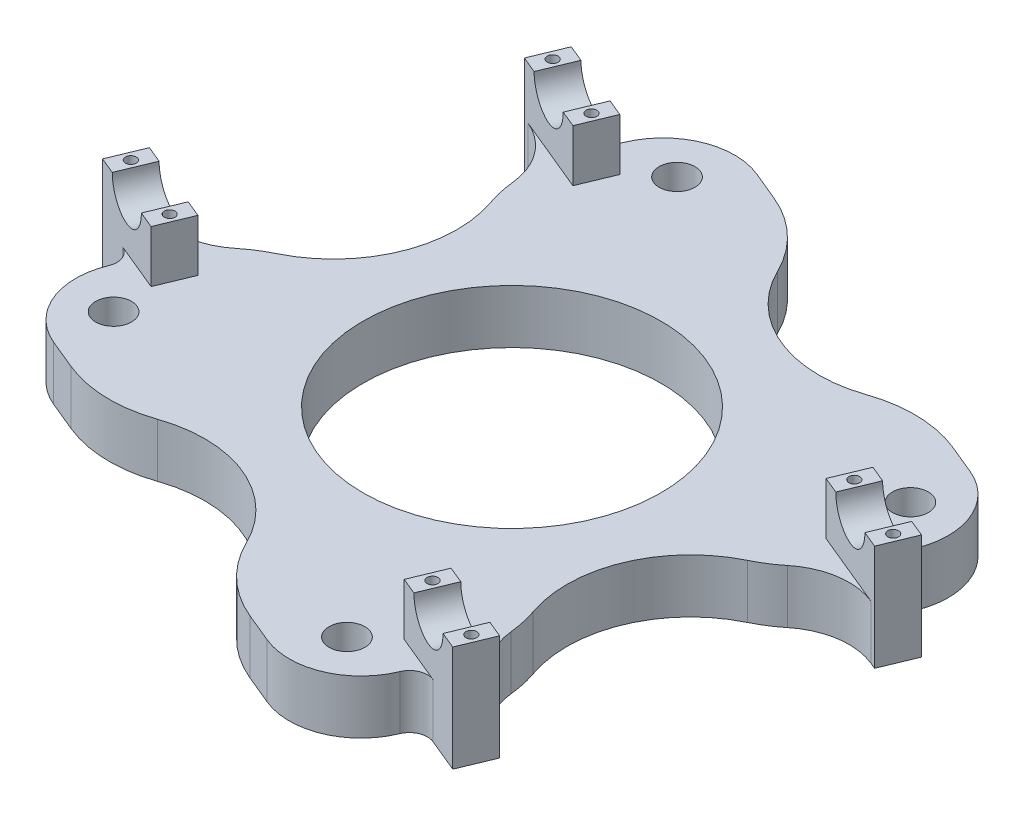
SolidWorks part; units mm, degrees
note: '?' marks a value the reader was unsure of.
material "6063-T5"
ref_plane "Front Plane" through (0, 0, 0) normal (0, 0, 1) x (1, 0, 0)
ref_plane "Top Plane" through (0, 0, 0) normal (0, 1, 0) x (1, 0, 0)
ref_plane "Right Plane" through (0, 0, 0) normal (1, 0, 0) x (0, 0, -1)
sketch "Sketch1" plane through (0, 0, 0) normal (0, 1, 0) x (1, 0, 0)
  circle A0 centre (0, 0) radius 41.5
  circle A1 centre (0, 0) radius 45.5
  dimension "D1" = 83
  dimension "D2" = 91
extrude "Boss-Extrude1" add sketch "Sketch1" along normal blind 156.5
ref_axis "Axis1" through (0, -7.993, 0) along (0, 1, 0)?
ref_plane "Plane1" through (0, 0, 0) normal (0.7071, 0, 0.7071) x (0, 1, 0)
sketch "Sketch3" plane through (0, 0, 0) normal (0.7071, 0, 0.7071) x (0, 1, 0)
  line L0 (0, 0) -> (152.25, 0)
  circle A0 centre (152.25, 0) radius 1.75
  dimension "D1" = 152.25
extrude "Cut-Extrude2" cut sketch "Sketch3" against normal through all and the other way through all contours A0
pattern_circular "CirPattern2" count 8 over 360 about axis through (0, -7.993, 0) along (0, 1, 0) of "Cut-Extrude2"
ref_plane "Plane2" through (0, 0, 0) normal (0.9239, 0, 0.3827) x (0, 1, 0)
ref_plane "Plane4" through (0, 0, 0) normal (0.3827, 0, -0.9239) x (0, 1, 0)
sketch "Sketch6" plane through (0, 0, 0) normal (0.9239, 0, 0.3827) x (0, 1, 0)
  line L0 (0, 0) -> (58, 0)
  line L1 (58, 0) -> (133, 0)
  line L3 (133, 0) -> (133, -38.75)
  line L4 (58, 38.516) -> (133, 38.516)
  line L5 (58, 38.516) -> (58, -38.75)
  line L6 (133, 38.516) -> (133, -38.75)
  line L7 (58, -38.75) -> (133, -38.75)
  line L8 (58, 38.516) -> (133, -38.75) construction
  line L9 (133, 38.516) -> (58, -38.75) construction
  point P6 (95.5, -0.117)
  dimension "D1" = 58
  dimension "D2" = 75
  dimension "D3" = 38.75
extrude "Cut-Extrude5" cut sketch "Sketch6" against normal through all contours L6 L4 L5 L7
fillet "Fillet1" radius 20 1 edges at (-3.0493, 58, -43.2058)
fillet "Fillet2" radius 20 1 edges at (-3.0493, 133, -43.2058)
fillet "Fillet3" radius 20 1 edges at (-33.0671, 58, 27.9926)
fillet "Fillet4" radius 20 1 edges at (-33.0671, 133, 27.9926)
sketch "Sketch11" plane through (0, 0, 0) normal (0.3827, 0, -0.9239) x (0, 1, 0)
  line L0 (0, 0) -> (0, 45.5)
  line L1 (0, 45.5) -> (15, 45.5)
  line L2 (156.5, 45.5) -> (0, 45.5) construction
  line L3 (15, 45.5) -> (15, 75)
  line L5 (0, 0) -> (15, 0)
  line L10 (0, 0) -> (0, 75)
  line L11 (0, 75) -> (15, 75)
  line L12 (15, 0) -> (15, 75)
  dimension "D1" = 15
  dimension "D2" = 29.5
extrude "Boss-Extrude2" add sketch "Sketch11" along normal blind 75 and the other way blind 75 contours L5 L12 L1 L0 | L11 L10 L1 L3
mirror "Mirror1" about plane through (0, 0, 0) normal (0.9239, 0, 0.3827) of "Boss-Extrude2"
sketch "Sketch12" plane through (0, 156.5, 0) normal (0, 1, 0) x (1, 0, 0)
  circle A0 centre (0, 0) radius 41.5
extrude "Cut-Extrude6" cut sketch "Sketch12" against normal through all
fillet "Fillet5" radius 20 1 edges at (97.9922, 7.5, -40.5897)
fillet "Fillet6" radius 20 1 edges at (40.5897, 7.5, 97.9922)
fillet "Fillet7" radius 20 1 edges at (-40.5897, 7.5, -97.9922)
fillet "Fillet8" radius 20 1 edges at (-97.9922, 7.5, 40.5897)
fillet "Fillet9" radius 25 1 edges at (0, 15, 45.5)
sketch "Sketch15" plane through (0, 15, 0) normal (0, 1, 0) x (1, 0, 0)
  line L0 (-90.3386, -22.1121) -> (-80.7715, 0.9849)
  line L1 (-90.3386, -22.1121) -> (-48.2434, 79.5146) construction
  line L2 (-48.2434, 79.5146) -> (-57.8105, 56.4176)
  line L4 (-80.7715, 0.9849) -> (-57.8105, 56.4176)
  arc A0 (-80.7715, 0.9849) -> (-57.8105, 56.4176) centre (-84.8971, 35.1655) ccw
  circle M3 centre (0, 0) radius 70.5
  line M4 (-48.2434, 79.5146) -> (-90.3386, -22.1121)
  dimension "D1" = 25
  dimension "D2" = 25
extrude "Cut-Extrude7" cut sketch "Sketch15" against normal through all and the other way through all contours A0 M3 | A0 M4 M3
fillet "Fillet10" radius 35 2 edges at (-75.4639, 15, -2.0543) (-80.7715, 7.5, -0.9849)
fillet "Fillet11" radius 35 3 edges at (-54.8137, 15, -51.9084) (-57.8105, 7.5, -56.4176) (-52.824, 18.6611, -22.6495)
pattern_circular "CirPattern4" count 4 over 360 about axis through (0, 0, 0) along (0, 1, 0) of "Cut-Extrude7", "Fillet10", "Fillet11"
sketch "Sketch16" plane through (0, 15, 0) normal (0, 1, 0) x (1, 0, 0)
  line L0 (-90.3386, -37.4195) -> (-78.5298, -32.5281)
  circle A0 centre (0, 0) radius 85
  arc A1 (-90.3386, -22.1121) -> (-79.5146, -48.2434) centre (-71.861, -29.7658) ccw construction
  circle A2 centre (-78.5298, -32.5281) radius 5
extrude "Cut-Extrude8" cut sketch "Sketch16" against normal through all contours A2
pattern_circular "CirPattern5" count 4 over 360 about axis through (0, 0, 0) along (0, 1, 0) of "Cut-Extrude8"
sketch "Sketch32" plane through (0, 15, 0) normal (0, 1, 0) x (1, 0, 0)
  circle A0 centre (0, 0) radius 138.736
extrude "Cut-Extrude20" cut sketch "Sketch32" along normal through all
ref_plane "Plane5" through (15.3073, 0, -36.9552) normal (0.3827, 0, -0.9239) x (0, 1, 0)
sketch "Sketch33" plane through (15.3073, 0, -36.9552) normal (0.3827, 0, -0.9239) x (0, 1, 0)
  line L0 (0, 0) -> (0, 77.69)
  line L1 (0, 65.19) -> (22, 65.19)
  line L2 (0, 90.19) -> (22, 90.19)
  line L3 (22, 65.19) -> (22, 90.19)
  line L4 (0, 90.19) -> (0, 65.19)
  line L5 (22, 65.19) -> (42, 65.19)
  line L6 (42, 65.19) -> (42, 90.19)
  line L7 (42, 90.19) -> (22, 90.19)
  circle A0 centre (0, 77.69) radius 12.5
  dimension "D2" = 22
  dimension "D4" = 20
  dimension "D1" = 77.69
  dimension "D3" = 22
  dimension "D5" = 20
extrude "Boss-Extrude3" add sketch "Sketch33" along normal blind 10 contours L0 A0 L4 | A0 L1 L3 L2 | L6 L7 L3 L5
sketch "Sketch34" plane through (15.3073, 0, -36.9552) normal (-0.3827, 0, 0.9239) x (0.9239, 0, 0.3827)
  line L0 (77.69, 42) -> (77.69, 29.5)
  line L1 (65.19, 42) -> (90.19, 42) construction
  circle A0 centre (77.69, 29.5) radius 7.5
  dimension "D2" = 15
  dimension "D1" = 12.5
extrude "Cut-Extrude21" cut sketch "Sketch34" against normal through all
sketch "Sketch39" plane through (0, 42, 0) normal (0, 1, 0) x (1, 0, 0)
  line L0 (75.535, 12.008) -> (98.632, 2.441)
  line L1 (98.632, 2.441) -> (102.4589, 11.6798)
  line L2 (102.4589, 11.6798) -> (79.3619, 21.2468)
  line L3 (79.3619, 21.2468) -> (75.535, 12.008)
extrude "Cut-Extrude24" cut sketch "Sketch39" against normal blind 12.5
sketch "Sketch41" plane through (0, 29.5, 0) normal (0, 1, 0) x (1, 0, 0)
  line L0 (77.4485, 16.6274) -> (82.0679, 14.714)
  line L1 (79.3619, 21.2468) -> (75.535, 12.008) construction
  line L2 (80.1544, 10.0946) -> (83.9813, 19.3334) construction
  line L3 (82.0679, 14.714) -> (95.9261, 8.9738)
  line L4 (97.8395, 13.5932) -> (94.0126, 4.3544) construction
  line L5 (95.9261, 8.9738) -> (100.5454, 7.0604)
  line L6 (98.632, 2.441) -> (102.4589, 11.6798) construction
  circle A0 centre (79.7582, 15.6707) radius 1.5
  circle A1 centre (98.2358, 8.0171) radius 1.5
extrude "Cut-Extrude25" cut sketch "Sketch41" against normal blind 12.5 contours A0 | A1
mirror "Mirror4" about plane through (0, 0, 0) normal (0.3827, 0, -0.9239) of "Cut-Extrude25", "Cut-Extrude24", "Cut-Extrude21", "Boss-Extrude3"
mirror "Mirror5" about plane through (0, 0, 0) normal (0.9239, 0, 0.3827) of "Mirror4", "Cut-Extrude25", "Cut-Extrude24", "Cut-Extrude21", "Boss-Extrude3"
fillet "Fillet12" radius 20 1 edges at (-84.0992, 7.5, 8.4607)
fillet "Fillet13" radius 20 1 edges at (-53.4845, 7.5, -65.4497)
fillet "Fillet14" radius 20 1 edges at (53.4845, 7.5, 65.4497)
fillet "Fillet15" radius 20 1 edges at (84.0992, 7.5, -8.4607)
fillet "Fillet16" radius 5 3 edges at (89.3818, 15, -19.8024) (89.3818, 0, -19.8024) (88.4251, 7.5, -17.4927)
fillet "Fillet18" radius 5 3 edges at (49.2001, 0, 77.2049) (49.2001, 15, 77.2049) (50.1568, 7.5, 74.8952)
fillet "Fillet19" radius 5 3 edges at (-89.3818, 15, 19.8024) (-89.3818, 0, 19.8024) (-88.4251, 7.5, 17.4927)
fillet "Fillet20" radius 5 3 edges at (-49.2001, 0, -77.2049) (-49.2001, 15, -77.2049) (-50.1568, 7.5, -74.8952)
